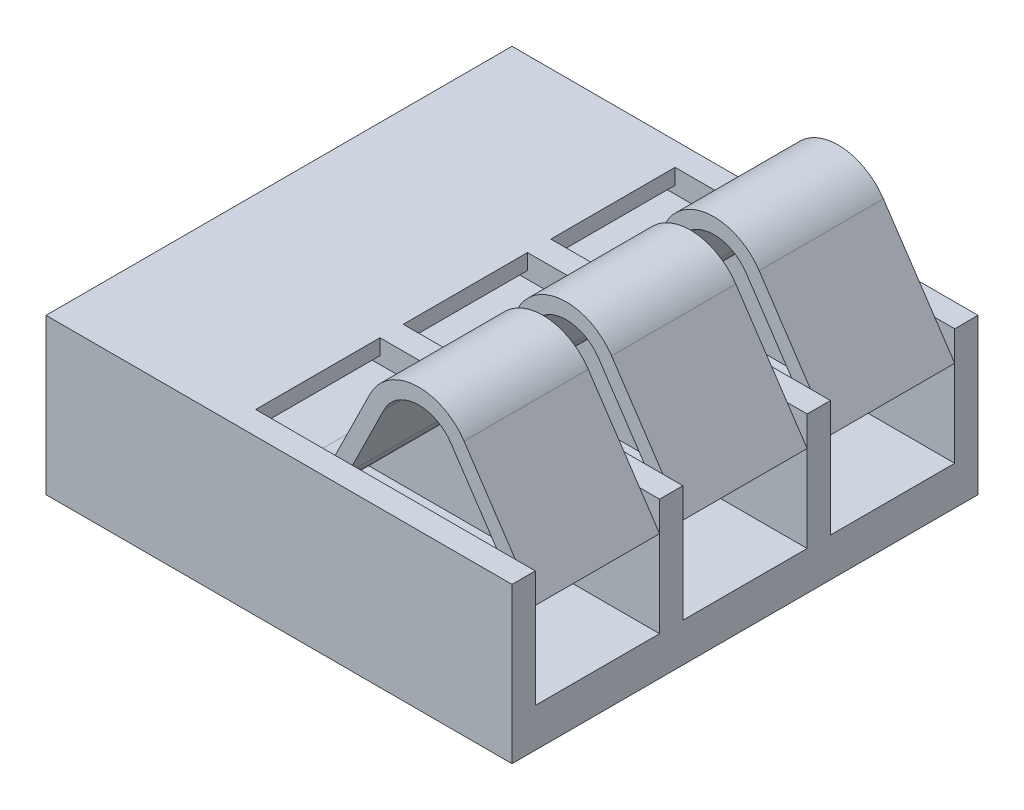
SolidWorks part; units mm, degrees
ref_plane "Front Plane" through (0, 0, 0) normal (0, 0, 1) x (1, 0, 0)
ref_plane "Top Plane" through (0, 0, 0) normal (0, 1, 0) x (1, 0, 0)
ref_plane "Right Plane" through (0, 0, 0) normal (1, 0, 0) x (0, 0, -1)
sketch "Sketch1" plane through (0, 0, 0) normal (0, 0, 1) x (1, 0, 0)
  line L0 (0.5, 0.5) -> (0.5, 1.5)
  line L1 (0, 0) -> (6, 0)
  line L2 (0, 0) -> (0, 2)
  line L3 (0, 2) -> (6, 2)
  line L4 (6, 0) -> (6, 2)
  line L5 (0.5, 1.5) -> (5.5, 1.5)
  line L6 (5.5, 0.5) -> (5.5, 1.5)
  line L7 (0.5, 0.5) -> (5.5, 0.5)
  line L8 (0.5, 1.5) -> (0.5, 2)
  line L9 (5.5, 0.5) -> (6, 0.5)
  dimension "D1" = 2
  dimension "D2" = 6
  dimension "D3" = 0.5
extrude "Boss-Extrude1" add sketch "Sketch1" along normal blind 6 contours L9 L7 L0 L8 L3 L2 L1 L4 region at (2.45, 0.45, 0)
sketch "Sketch2" plane through (0, 0, 0) normal (0, 0, 1) x (1, 0, 0)
  line L0 (6, 1.615) -> (5.082, 2.9889)
  line L1 (3.8722, 2.9096) -> (3.4132, 1.9788)
  line L2 (2.9647, 1.7) -> (1.4, 1.7)
  line L3 (0.7, 1) -> (0.7, 0.5)
  line L4 (0.5, 0.5) -> (6, 0.5) construction
  line L5 (0.7, 0.5) -> (6, 0.5)
  line L6 (0.9, 0.5) -> (0.9, 1)
  line L7 (1.4, 1.5) -> (2.9647, 1.5)
  line L8 (3.5925, 1.8904) -> (4.0516, 2.8212)
  line L9 (4.9157, 2.8778) -> (5.8337, 1.5039)
  line L10 (5.8337, 1.5039) -> (6, 1.615)
  line L11 (0, 0) -> (6, 0) construction
  line L12 (0.5, 0.5) -> (0.5, 2) construction
  line L13 (6, 0) -> (6, 0.5) construction
  line L14 (0, 0) -> (0, 2) construction
  line L15 (4.5, 3.3) -> (50004.5, 3.3) construction
  arc A0 (0.9, 1) -> (1.4, 1.5) centre (1.4, 1) cw
  arc A1 (1.4, 1.7) -> (0.7, 1) centre (1.4, 1) ccw
  arc A2 (5.082, 2.9889) -> (3.8722, 2.9096) centre (4.5, 2.6) ccw
  arc A3 (4.0516, 2.8212) -> (4.9157, 2.8778) centre (4.5, 2.6) cw
  arc A4 (3.4132, 1.9788) -> (2.9647, 1.7) centre (2.9647, 2.2) cw
  arc A5 (2.9647, 1.5) -> (3.5925, 1.8904) centre (2.9647, 2.2) ccw
  point P27 (4.4085, 3.997)
  point P34 (3.4, 1.5)
  dimension "D7" = 0.5
  dimension "D8" = 0.7
  dimension "D11" = 0.7
  dimension "D12" = 0.5
  dimension "D13" = 0.5
  dimension "D14" = 0.7
  dimension "D1" = 0.2
  dimension "D2" = 0.2
  dimension "D3" = 0.2
  dimension "D4" = 0.2
  dimension "D5" = 1.7
  dimension "D6" = 0.2
  dimension "D9" = 2
  dimension "D10" = 3.3
  dimension "D15" = 4.5
  dimension "D16" = 60
extrude "Boss-Extrude2" add sketch "Sketch2" along normal blind 1.6 from offset 0.3 contours L7 A5 L8 A3 L9 L10 L0 A2 L1 A4 L2 A1 L3 L5 L6 A0 region at (5.8836, 1.6093, 0)
extrude "Boss-Extrude3" add sketch "Sketch1<3>" along normal blind 0.3 contours L0 L7 L6 L5 | L6 L9 L4 L3 L8 L5 region at (3, 1, 0) region at (3.6346, 1.6346, 0)
sketch "Sketch1<3>" plane through (0, 0, 0) normal (0, 0, 1) x (1, 0, 0) same geometry as "Sketch1"
extrude "Boss-Extrude4" add sketch "Sketch1<5>" along normal blind 0.3 from surface contours L6 L9 L4 L3 L8 L5 | L0 L7 L6 L5 region at (3, 1, 0) region at (3.6346, 1.6346, 0) starting at face at (3.0311, 1.7924, 1.9)
sketch "Sketch1<5>" plane through (0, 0, 0) normal (0, 0, 1) x (1, 0, 0) same geometry as "Sketch1"
extrude "Boss-Extrude5" add sketch "Sketch2<3>" along normal blind 1.6 from surface contours L7 A5 L8 A3 L9 L10 L0 A2 L1 A4 L2 A1 L3 L5 L6 A0 region at (5.8836, 1.6093, 0) starting at face at (3.25, 1.25, 2.2)
sketch "Sketch2<3>" plane through (0, 0, 0) normal (0, 0, 1) x (1, 0, 0) same geometry as "Sketch2"
extrude "Boss-Extrude6" add sketch "Sketch1<6>" along normal blind 0.3 from surface contours L0 L7 L6 L5 | L6 L9 L4 L3 L8 L5 region at (3, 1, 0) region at (3.6346, 1.6346, 0) starting at face at (3.0311, 1.7924, 3.8)
sketch "Sketch1<6>" plane through (0, 0, 0) normal (0, 0, 1) x (1, 0, 0) same geometry as "Sketch1"
extrude "Boss-Extrude7" add sketch "Sketch2<4>" along normal blind 1.6 from surface contours L7 A5 L8 A3 L9 L10 L0 A2 L1 A4 L2 A1 L3 L5 L6 A0 region at (5.8836, 1.6093, 0) starting at face at (3.25, 1.25, 4.1)
sketch "Sketch2<4>" plane through (0, 0, 0) normal (0, 0, 1) x (1, 0, 0) same geometry as "Sketch2"
extrude "Boss-Extrude8" add sketch "Sketch1<7>" along normal blind 0.3 from surface contours L6 L9 L4 L3 L8 L5 | L0 L7 L6 L5 region at (3, 1, 0) region at (3.6346, 1.6346, 0) starting at face at (3.0311, 1.7924, 5.7)
sketch "Sketch1<7>" plane through (0, 0, 0) normal (0, 0, 1) x (1, 0, 0) same geometry as "Sketch1"
sketch "Sketch3" plane through (0, 2, 0) normal (0, 1, 0) x (1, 0, 0)
  line L0 (0, -6) -> (6, -6) construction
  line L1 (0, 0) -> (2.4, 0)
  line L2 (0, 0) -> (0, -6)
  line L3 (0, -6) -> (2.4, -6)
  line L4 (2.4, 0) -> (2.4, -6)
  dimension "D1" = 2.4
extrude "Boss-Extrude9" add sketch "Sketch3" against normal blind 0.2
ref_plane "Plane1" through (0, 3.3, 0) normal (0, 1, 0) x (1, 0, 0)
